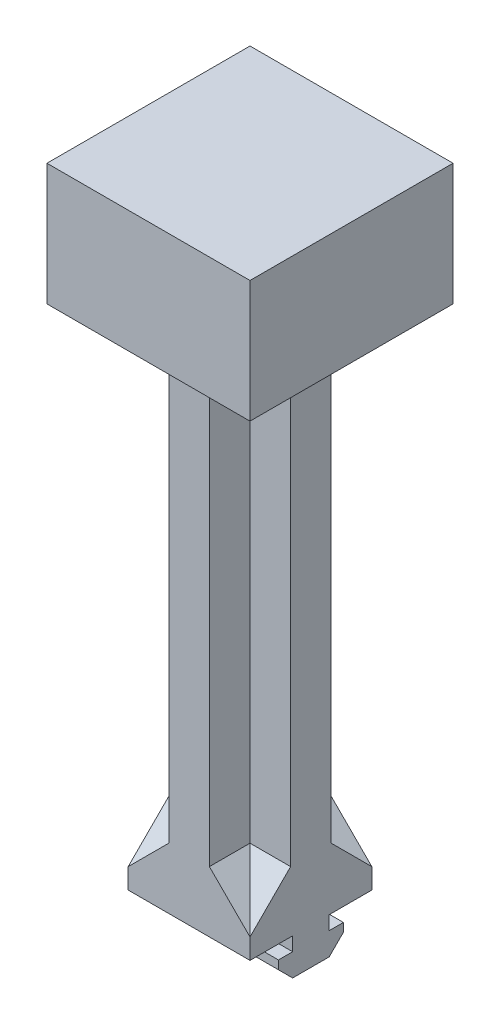
SolidWorks part; units mm, degrees
ref_plane "Front Plane" through (0, 0, 0) normal (0, 0, 1) x (1, 0, 0)
ref_plane "Top Plane" through (0, 0, 0) normal (0, 1, 0) x (1, 0, 0)
ref_plane "Right Plane" through (0, 0, 0) normal (1, 0, 0) x (0, 0, -1)
sketch "Sketch1" plane through (0, 0, 0) normal (0, 0, 1) x (1, 0, 0)
  line L1 (0, 0) -> (31.75, 0)
  line L2 (0, 0) -> (0, 19.05)
  line L3 (0, 19.05) -> (31.75, 19.05)
  line L4 (31.75, 0) -> (31.75, 19.05)
  dimension "D1" = 31.75
  dimension "D2" = 19.05
extrude "Boss-Extrude1" add sketch "Sketch1" along normal blind 31.75
shell "Shell1" thickness 3.175 removed face at (15.875, 9.525, 0)
sketch "Sketch2" plane through (0, 0, 0) normal (0, -1, 0) x (1, 0, 0)
  line L0 (12.7, 25.4) -> (12.7, 19.05)
  line L4 (12.7, 19.05) -> (6.35, 19.05)
  line L5 (6.35, 19.05) -> (6.35, 12.7)
  line L6 (6.35, 12.7) -> (12.7, 12.7)
  line L7 (12.7, 12.7) -> (12.7, 6.35)
  line L13 (12.7, 6.35) -> (19.05, 6.35)
  line L14 (19.05, 6.35) -> (19.05, 12.7)
  line L15 (19.05, 12.7) -> (25.4, 12.7)
  line L16 (25.4, 12.7) -> (25.4, 19.05)
  line L17 (25.4, 19.05) -> (19.05, 19.05)
  line L18 (19.05, 19.05) -> (19.05, 25.4)
  line L19 (19.05, 25.4) -> (12.7, 25.4)
  line L20 (0, 31.75) -> (31.75, 0) construction
  line L21 (0, 0) -> (31.75, 31.75) construction
  dimension "D1" = 6.35
extrude "Boss-Extrude2" add sketch "Sketch2" along normal blind 76.2
sketch "Sketch3" plane through (0, 0, 0) normal (1, 0, 0) x (0, 0, -1)
  line L5 (-10.795, -81.534) -> (-10.795, -82.8675)
  line L6 (-10.795, -82.8675) -> (-13.0175, -85.09)
  line L7 (-13.0175, -85.09) -> (-18.7325, -85.09)
  line L8 (-18.7325, -85.09) -> (-20.955, -82.8675)
  line L9 (-20.955, -82.8675) -> (-20.955, -81.534)
  line L14 (-6.35, -76.2) -> (-25.4, -76.2)
  line L15 (-25.4, -76.2) -> (-25.4, -79.375)
  line L16 (-25.4, -79.375) -> (-18.7325, -79.375)
  line L17 (-18.7325, -79.375) -> (-18.7325, -81.534)
  line L18 (-18.7325, -81.534) -> (-20.955, -81.534)
  line L19 (-13.0175, -79.375) -> (-13.0175, -81.534)
  line L20 (-13.0175, -81.534) -> (-10.795, -81.534)
  line L21 (-6.35, -76.2) -> (-6.35, -79.375)
  line L22 (-13.0175, -79.375) -> (-6.35, -79.375)
  line L23 (-25.4, -76.2) -> (-25.4, 0) construction
  line L24 (-19.05, -76.2) -> (-25.4, -76.2) construction
  line L26 (-6.35, -76.2) -> (-6.35, 0) construction
  dimension "D1" = 5.715
  dimension "D3" = 10.16
  dimension "D4" = 2.159
  dimension "D5" = 5.715
  dimension "D6" = 3.175
extrude "Boss-Extrude3" add sketch "Sketch3" against normal up to surface (-6.35 mm away) from surface up to face at (6.35, -38.1, 15.875) starting at face at (25.4, -38.1, 15.875)
chamfer "Chamfer1" distance 6.35 angle 45 16 edges at (9.525, -76.2, 19.05) (12.7, -76.2, 22.225) (22.225, -76.2, 19.05) (19.05, -76.2, 22.225) (22.225, -76.2, 12.7) (19.05, -76.2, 9.525) (9.525, -76.2, 12.7) (12.7, -76.2, 9.525) (12.7, 0, 22.225) (9.525, 0, 19.05) (22.225, 0, 19.05) (19.05, 0, 22.225) (19.05, 0, 9.525) (22.225, 0, 12.7) (12.7, 0, 9.525) (9.525, 0, 12.7)
